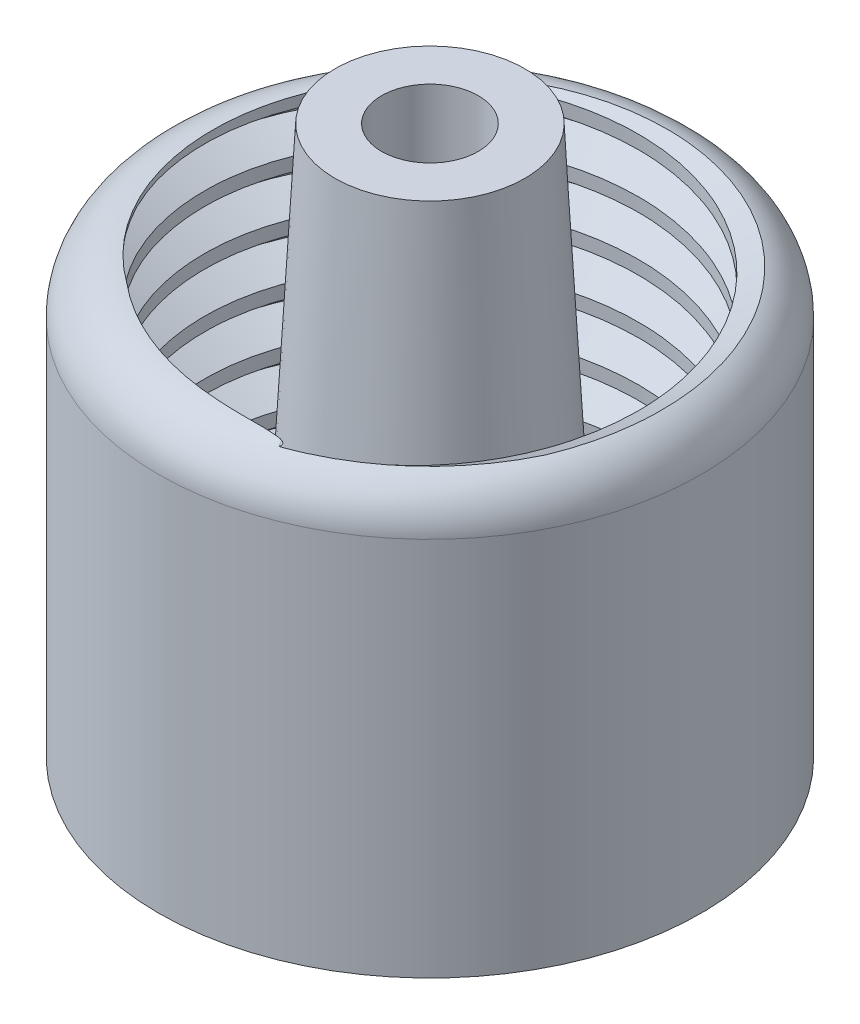
SolidWorks part; units mm, degrees
ref_plane "Front Plane" through (0, 0, 0) normal (0, 0, 1) x (1, 0, 0)
ref_plane "Top Plane" through (0, 0, 0) normal (0, 1, 0) x (1, 0, 0)
ref_plane "Right Plane" through (0, 0, 0) normal (1, 0, 0) x (0, 0, -1)
sketch "Sketch1" plane through (0, 0, 0) normal (0, 1, 0) x (1, 0, 0)
  circle A0 centre (0, 0) radius 5
  dimension "D1" = 10
extrude "Boss-Extrude1" add sketch "Sketch1" along normal blind 8
sketch "Sketch2" plane through (0, 8, 0) normal (0, 1, 0) x (1, 0, 0)
  circle A0 centre (0, 0) radius 4
  dimension "D1" = 8
extrude "Cut-Extrude1" cut sketch "Sketch2" against normal blind 5.4
sketch "Sketch3" plane through (0, 2.6, 0) normal (0, 1, 0) x (1, 0, 0)
  circle A0 centre (0, 0) radius 1.75
  dimension "D1" = 3.5
extrude "Boss-Extrude2" add sketch "Sketch3" along normal blind 7.5
sketch "Sketch4" plane through (0, 10.1, 0) normal (0, 1, 0) x (1, 0, 0)
  circle A0 centre (0, 0) radius 0.891
  dimension "D1" = 1.782
extrude "Cut-Extrude2" cut sketch "Sketch4" against normal blind 12.834
fillet "Fillet4" radius 1 1 edges at (0, 8, 5)
draft "Draft2" type of draft neutral plane draft angle 3 faces to draft 1 face at (0, 10.1, 1.75) neutral plane through (0, 10.1, 0) neutral plane normal (0, 1, 0) parameters "D1"=3
thread "Thread1" pitch 1 method cut profile "Thread Profile1" start angle 0, offset 1, length 10, pitch 1, diameter 8
ref_plane "Plane1" through (4, 1.6, 0) normal (0, 0, 1) x (1, 0, 0)
sketch "Thread Profile1" plane through (4, 1.6, 0) normal (0, 0, 1) x (1, 0, 0)
  line L0 (0, 0) -> (0, 1) construction
  line L1 (0, 0) -> (0.5413, 0.3125)
  line L2 (0.5413, 0.3125) -> (0.5413, 0.4375)
  line L3 (0.5413, 0.4375) -> (0, 0.75)
  line L4 (0.5413, 0.375) -> (0, 0.375) construction
  line L11 (0, 0) -> (0, 0.75)
  point P2 (0, 0)
  dimension "Pitch" = 1
  dimension "Profile_Angle" = 60
  dimension "Profile_Land" = 0.125
  dimension "Profile_Height" = 0.5413
